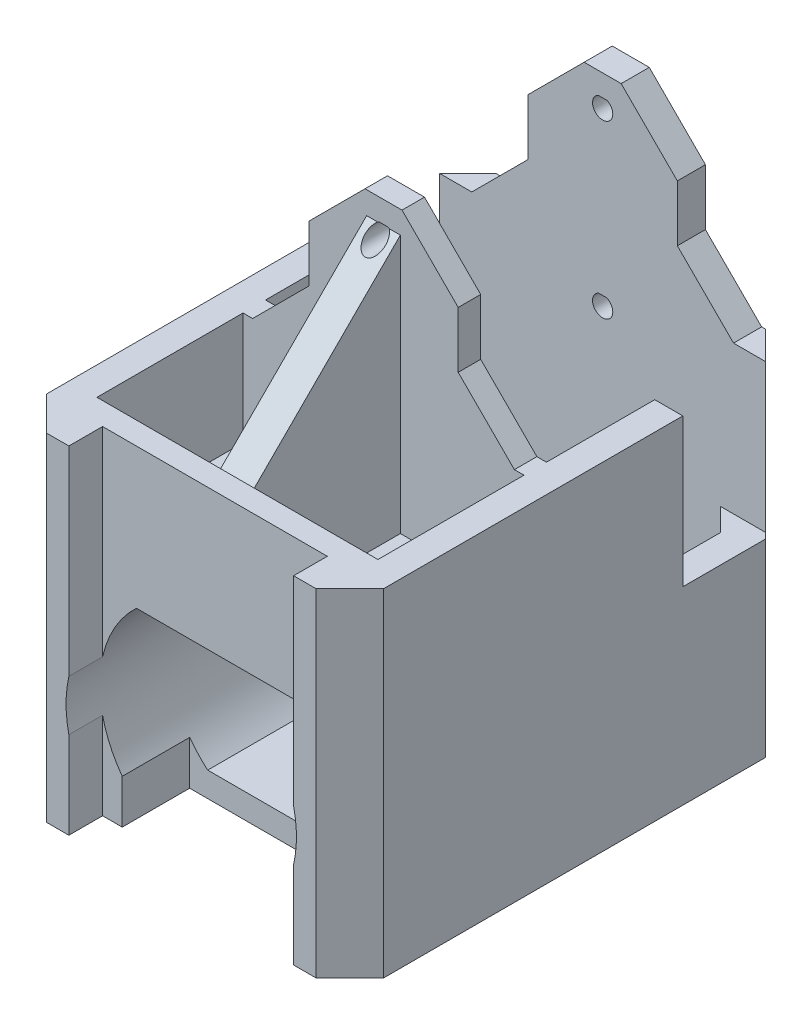
SolidWorks part; units mm, degrees
ref_plane "Front Plane" through (0, 0, 0) normal (0, 0, 1) x (1, 0, 0)
ref_plane "Top Plane" through (0, 0, 0) normal (0, 1, 0) x (1, 0, 0)
ref_plane "Right Plane" through (0, 0, 0) normal (1, 0, 0) x (0, 0, -1)
sketch "Sketch1" plane through (0, 0, 0) normal (0, 0, 1) x (1, 0, 0)
  line L1 (-15, -20) -> (15, -20)
  line L2 (-15, -20) -> (-15, 20)
  line L3 (-15, 20) -> (15, 20)
  line L4 (15, -20) -> (15, 20)
  line L5 (-15, -20) -> (15, 20) construction
  line L6 (-15, 20) -> (15, -20) construction
  point P0 (0, 0)
  dimension "D1" = 30
  dimension "D2" = 40
extrude "Boss-Extrude1" add sketch "Sketch1" along normal blind 40
sketch "Sketch2" plane through (0, 0, 40) normal (0, 0, 1) x (1, 0, 0)
  line L5 (-6.9866, -2.5) -> (6.9866, -2.5)
  line L7 (-6.6464, -17.803) -> (6.6464, -17.803)
  arc A4 (-6.9866, -2.5) -> (-6.6464, -17.803) centre (0, -10) ccw
  arc A5 (6.6464, -17.803) -> (6.9866, -2.5) centre (0, -10) ccw
  point P0 (0, -10)
  dimension "D2" = 20.5
extrude "Cut-Extrude1" cut sketch "Sketch2" against normal blind 35
sketch "Sketch4" plane through (0, 20, 0) normal (0, 1, 0) x (1, 0, 0)
  line L1 (-12.5, -37.5) -> (12.5, -37.5)
  line L2 (-12.5, -37.5) -> (-12.5, -2.5)
  line L3 (-12.5, -2.5) -> (12.5, -2.5)
  line L4 (12.5, -37.5) -> (12.5, -2.5)
  point P0 (0, -20)
  dimension "D1" = 25
  dimension "D2" = 35
extrude "Cut-Extrude3" cut sketch "Sketch4" against normal blind 20
sketch "Sketch5" plane through (0, 0, 0) normal (0, 1, 0) x (1, 0, 0)
  line L0 (12.5, -37.5) -> (12.5, -2.5) construction
  line L1 (-12.5, -2.5) -> (12.5, -2.5)
  line L2 (-12.5, -2.5) -> (-12.5, -20)
  line L3 (-12.5, -20) -> (12.5, -20)
  line L4 (12.5, -2.5) -> (12.5, -20)
extrude "Cut-Extrude4" cut sketch "Sketch5" against normal blind 20
sketch "Sketch13" plane through (0, 0, 0) normal (0, 1, 0) x (1, 0, 0)
  line L0 (12.5, -37.5) -> (12.5, -20) construction
  line L1 (-12.5, -20) -> (12.5, -20)
  line L2 (-12.5, -20) -> (-12.5, -22.0007)
  line L3 (-12.5, -22.0007) -> (12.5, -22.0007)
  line L4 (12.5, -20) -> (12.5, -22.0007)
extrude "Boss-Extrude3" add sketch "Sketch13" along normal up to surface (20 mm away) up to face at (0, 20, 20)
sketch "Sketch8" plane through (0, 0, 40) normal (0, 0, 1) x (1, 0, 0)
  line L0 (-0.5467, -9.1627) -> (0.5467, -9.1627)
  arc A3 (-0.5467, -9.1627) -> (0.5467, -9.1627) centre (0, -10.2278) ccw
extrude "Cut-Extrude5" cut sketch "Sketch8" against normal up to surface (40 mm away) up to face at (0, 0, 0)
sketch "Sketch9" plane through (0, 0, 0) normal (0, 0, -1) x (-1, 0, 0)
  line L6 (-0.3543, 7.8496) -> (0.3543, 7.8496)
  arc A2 (-0.3543, 7.8496) -> (0.3543, 7.8496) centre (0, 7.0222) ccw
extrude "Cut-Extrude6" cut sketch "Sketch9" against normal up to surface (40 mm away) up to face at (0, -10.1897, 40)
sketch "Sketch10" plane through (0, 0, 40) normal (0, 0, 1) x (1, 0, 0)
  line L0 (15, -20) -> (15, 20) construction
  line L1 (-15, 20) -> (15, 20)
  line L2 (-15, 20) -> (-15, 10)
  line L3 (-15, 10) -> (15, 10)
  line L4 (15, 20) -> (15, 10)
  dimension "D1" = 10
extrude "Cut-Extrude9" cut sketch "Sketch10" against normal up to surface (40 mm away) up to face at (0, 6.9859, 0)
chamfer "Chamfer2" distance 3 angle 45 4 edges at (15, -5, 0) (15, -5, 40) (-15, -5, 40) (-15, -5, 0)
sketch "Sketch16" plane through (-12.5, 0, 0) normal (1, 0, 0) x (0, 0, -1)
  line L1 (-2.5, 10) -> (-9.5368, 10)
  line L2 (-2.5, 10) -> (-2.5, -3.1649)
  line L6 (-9.5368, -3.1649) -> (-2.5, -3.1649)
  line L7 (-9.5368, -3.1649) -> (-10.3664, -3.1649)
  line L8 (-10.3664, -3.1649) -> (-10.3664, 10)
  line L9 (-3, 10) -> (-37, 10) construction
  line L10 (-10.3664, 10) -> (-9.5368, 10)
extrude "Cut-Extrude10" cut sketch "Sketch16" against normal mid plane 57
sketch "Sketch17" plane through (0, 10, 0) normal (0, 1, 0) x (1, 0, 0)
  line L0 (12.5, -37.5) -> (12.5, -22.0007) construction
  line L1 (-12.5, -37.5) -> (12.5, -37.5)
  line L2 (-12.5, -37.5) -> (-12.5, -35)
  line L3 (-12.5, -35) -> (12.5, -35)
  line L4 (12.5, -37.5) -> (12.5, -35)
  dimension "D1" = 2.5
extrude "Boss-Extrude4" add sketch "Sketch17" against normal up to surface (10 mm away) up to face at (0, 0, 29.7504)
sketch "Sketch18" plane through (0, 10, 0) normal (0, 1, 0) x (1, 0, 0)
  line L0 (-10, -40) -> (10, -40)
  line L1 (-12, -40) -> (12, -40) construction
  line L5 (-10, -40) -> (10, -40)
  line L6 (-10, -40) -> (-10, -37)
  line L7 (-10, -37) -> (10, -37)
  line L8 (10, -40) -> (10, -37)
  point P5 (0, -40)
  line M15 (-12, -40) -> (12, -40)
  dimension "D1" = 20
  dimension "D2" = 3
extrude "Cut-Extrude13" cut sketch "Sketch18" against normal up to surface (30 mm away) contours L8 L7 L6 M15 region at (0, 10, 38.5) up to face at (0, -20, 11.25)
sketch "Sketch19" plane through (0, -20, 0) normal (0, -1, 0) x (1, 0, 0)
  line L0 (-8.25, 37) -> (8.25, 37)
  line L1 (10, 37) -> (-10, 37) construction
  line L5 (-8.25, 37) -> (8.25, 37)
  line L6 (-8.25, 37) -> (-8.25, 31)
  line L7 (-8.25, 31) -> (8.25, 31)
  line L8 (8.25, 37) -> (8.25, 31)
  point P5 (0, 37)
  line M18 (10, 37) -> (-10, 37)
  dimension "D1" = 16.5
  dimension "D2" = 6
extrude "Cut-Extrude14" cut sketch "Sketch19" against normal blind 10 contours L8 L6 L7 M18 region at (0, -20, 34)
sketch "Sketch20" plane through (0, 0, 20) normal (0, 0, -1) x (-1, 0, 0)
  line L0 (10.25, -10) -> (12.5, -10)
  line L1 (-12.5, -10) -> (-10.25, -10)
  line L2 (-12.5, -10) -> (-12.5, -20)
  line L3 (-12.5, -20) -> (12.5, -20)
  line L4 (12.5, -20) -> (12.5, 10)
  line L5 (12.5, 10) -> (-12.5, 10)
  line L6 (-12.5, 10) -> (-12.5, -20)
  line L7 (-12.5, -20) -> (12.5, -20)
  line L8 (12.5, -20) -> (12.5, -10)
  line L10 (-12.5, -10) -> (-12.5, -20)
  line L11 (-12.5, -20) -> (12.5, -20)
  line L12 (12.5, -10) -> (12.5, -20)
  line L13 (-6.6464, -17.803) -> (6.6464, -17.803)
  arc A0 (6.6464, -17.803) -> (6.9866, -2.5) centre (0, -10) ccw construction
  arc A1 (6.6464, -17.803) -> (10.25, -10) centre (0, -10) ccw
  arc A2 (-6.9866, -2.5) -> (-6.6464, -17.803) centre (0, -10) ccw construction
  arc A3 (-10.25, -10) -> (-6.6464, -17.803) centre (0, -10) ccw
  line M7 (12.5, -20) -> (12.5, 10)
  line M9 (-12.5, 10) -> (-12.5, -20)
  line M10 (-12.5, -20) -> (12.5, -20)
  line M11 (6.6464, -17.803) -> (-6.6464, -17.803)
  arc M12 (-6.6464, -17.803) -> (-6.9866, -2.5) centre (0, -10) cw
  arc M14 (6.9866, -2.5) -> (6.6464, -17.803) centre (0, -10) cw
  dimension "D1" = 0
extrude "Boss-Extrude5" add sketch "Sketch20" along normal blind 8.5 contours L1 L0 M9 M10 M7 M14 M11 M12 region at (-11.375, -10.2693, 20)
sketch "Sketch22" plane through (0, 0, 11.5) normal (0, 0, -1) x (-1, 0, 0)
  line L0 (12.5, -20) -> (12.5, -10) construction
  line L1 (-12.5, -20) -> (12.5, -20)
  line L2 (-12.5, -20) -> (-12.5, -15)
  line L3 (-12.5, -15) -> (12.5, -15)
  line L4 (12.5, -20) -> (12.5, -15)
extrude "Boss-Extrude6" add sketch "Sketch22" along normal blind 1
sketch "Sketch23" plane through (0, 10, 0) normal (0, 1, 0) x (1, 0, 0)
  line L0 (-12.5, -10.5) -> (12.5, -10.5) construction
  line L3 (-6.6464, -22.0007) -> (6.6464, -22.0007)
  line L4 (6.6464, 0) -> (6.6464, -2.5)
  line L5 (-6.6464, 0) -> (-6.6464, -2.5)
  line L6 (-6.6464, -2.5) -> (0, -2.5)
  line L7 (-12.5, -22.0007) -> (12.5, -22.0007) construction
  line L8 (12.5, -22.0007) -> (-12.5, -22.0007) construction
  line L9 (-6.6464, -20) -> (6.6464, -20)
  line L10 (-12.5, -20) -> (12.5, -20) construction
  line L11 (-6.6464, 0) -> (6.6464, 0)
  line L12 (-12, 0) -> (12, 0) construction
  line L14 (14.5, -2.5) -> (-14.5, -2.5) construction
  line L15 (0, -2.5) -> (6.6464, -2.5)
  line L17 (-6.6464, -20) -> (-6.6464, -22.0007)
  line L18 (6.6464, -20) -> (6.6464, -22.0007)
  point P0 (0, -10.5)
  point P16 (0, -20)
  point P21 (0, 0)
extrude "Boss-Extrude7" add sketch "Sketch23" along normal blind 15
chamfer "Chamfer4" distance 5 angle 45 4 edges at (-6.6464, 10, 21.0004) (-6.6464, 10, 1.25) (6.6464, 10, 21.0004) (6.6464, 10, 1.25)
chamfer "Chamfer6" distance 5 angle 45 4 edges at (-6.6464, 25, 1.25) (-6.6464, 25, 21.0004) (6.6464, 25, 1.25) (6.6464, 25, 21.0004)
sketch "Sketch30" plane through (0, 0, 0) normal (0, 1, 0) x (1, 0, 0)
  line L3 (-12.5, -22.0007) -> (12.5, -22.0007) construction
  line L4 (-1.5, -35) -> (1.5, -35)
  line L5 (-1.5, -35) -> (-1.5, -22.0007)
  line L6 (-1.5, -22.0007) -> (1.5, -22.0007)
  line L7 (1.5, -35) -> (1.5, -22.0007)
  point P6 (0, -28.5004)
  dimension "D1" = 3
extrude "Boss-Extrude8" add sketch "Sketch30" along normal blind 24
chamfer "Chamfer10" distance 14 1 edges at (0, 24, 35)
sketch "Sketch29" plane through (0, 0, 0) normal (0, 0, -1) x (-1, 0, 0)
  line L2 (-0.4034, 23.0745) -> (0.4034, 23.0745)
  arc A1 (-0.4034, 23.0745) -> (0.4034, 23.0745) centre (0, 22.27) ccw
extrude "Cut-Extrude15" cut sketch "Sketch29" against normal blind 25
chamfer "Chamfer11" distance 2 angle 45 2 edges at (12.5, -11.5824, 2.5) (-12.5, -11.5824, 2.5)
